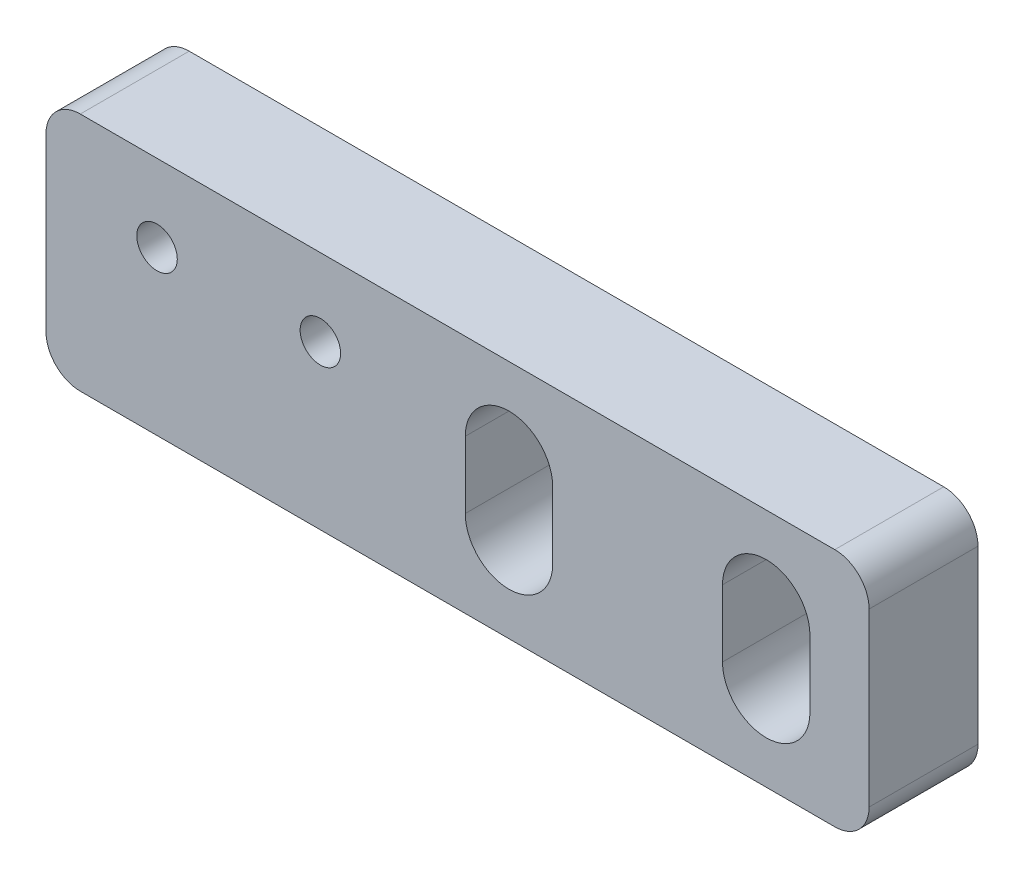
SolidWorks part; units mm, degrees
ref_plane "Front Plane" through (0, 0, 0) normal (0, 0, 1) x (1, 0, 0)
ref_plane "Top Plane" through (0, 0, 0) normal (0, 1, 0) x (1, 0, 0)
ref_plane "Right Plane" through (0, 0, 0) normal (1, 0, 0) x (0, 0, -1)
sketch "Sketch1" plane through (0, 0, 0) normal (0, 0, 1) x (1, 0, 0)
  line L55 (399.0337, 239.3839) -> (443.0337, 239.3839)
  line L63 (443.0337, 253.3839) -> (399.0337, 253.3839)
  line L88 (397.0337, 251.3839) -> (397.0337, 241.3839)
  line L90 (421.4837, 248.3339) -> (421.4837, 244.4339)
  line L91 (426.5837, 244.4339) -> (426.5837, 248.3339)
  line L93 (436.4837, 248.3339) -> (436.4837, 244.4339)
  line L94 (441.5837, 244.4339) -> (441.5837, 248.3339)
  line L95 (445.0337, 241.3839) -> (445.0337, 251.3839)
  arc A130 (426.5837, 248.3339) -> (421.4837, 248.3339) centre (424.0337, 248.3339) ccw
  arc A131 (421.4837, 244.4339) -> (426.5837, 244.4339) centre (424.0337, 244.4339) ccw
  arc A132 (441.5837, 248.3339) -> (436.4837, 248.3339) centre (439.0337, 248.3339) ccw
  arc A133 (436.4837, 244.4339) -> (441.5837, 244.4339) centre (439.0337, 244.4339) ccw
  circle A140 centre (403.5087, 248.8839) radius 2.286
  circle A141 centre (413.0337, 248.8839) radius 2.286
  arc A142 (399.0337, 253.3839) -> (397.0337, 251.3839) centre (399.0337, 251.3839) ccw
  arc A143 (397.0337, 241.3839) -> (399.0337, 239.3839) centre (399.0337, 241.3839) ccw
  arc A144 (445.0337, 251.3839) -> (443.0337, 253.3839) centre (443.0337, 251.3839) ccw
  arc A145 (443.0337, 239.3839) -> (445.0337, 241.3839) centre (443.0337, 241.3839) ccw
  circle A148 centre (403.5087, 248.8839) radius 1.181
  circle A149 centre (413.0337, 248.8839) radius 1.181
extrude "Boss-Extrude1" add sketch "Sketch1" along normal blind 6.35 contours L55 A145 L95 A144 L63 A142 L88 A143 A131 L90 A130 L91 A133 L93 A132 L94 A140 A141 | A141 A149 | A140 A148 region at (420.2633, 246.236, 0) region at (401.2874, 248.8839, 0) region at (410.8124, 248.8839, 0)
extrude "Cut-Extrude1" cut sketch "Sketch1<3>" along normal blind 3.175 contours A140 A148 | A141 A149 region at (401.2874, 248.8839, 0) region at (410.8124, 248.8839, 0)
sketch "Sketch1<3>" plane through (0, 0, 0) normal (0, 0, 1) x (1, 0, 0) same geometry as "Sketch1"
